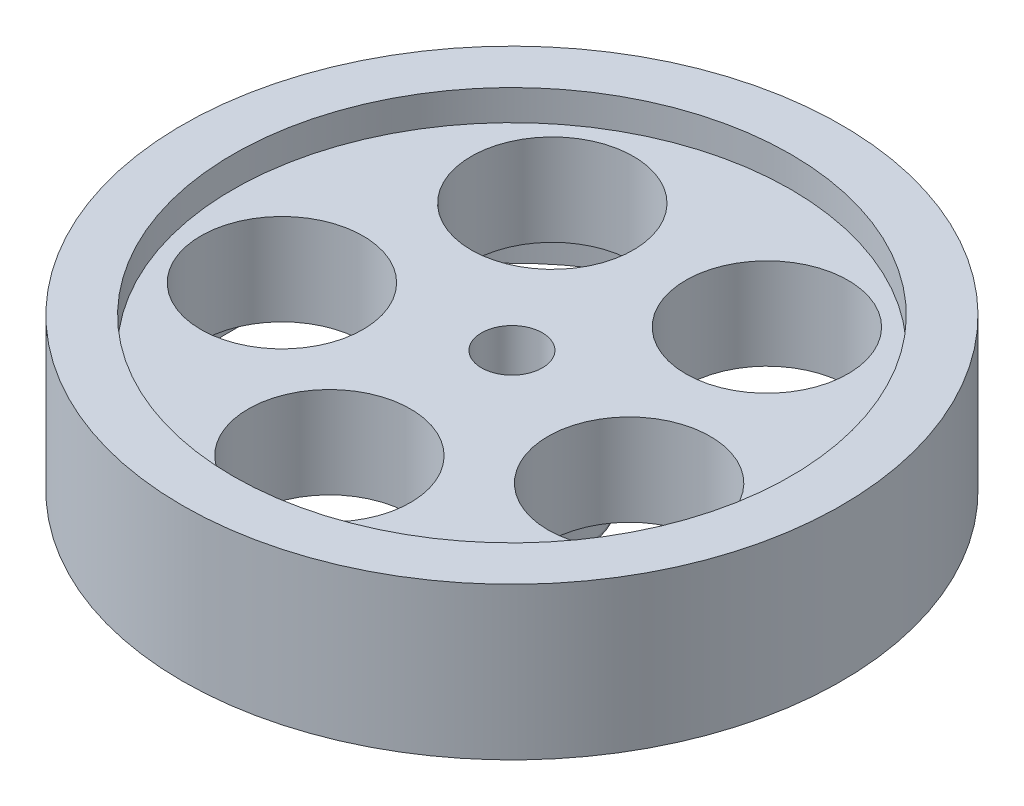
SolidWorks part; units mm, degrees
ref_plane "Front Plane" through (0, 0, 0) normal (0, 0, 1) x (1, 0, 0)
ref_plane "Top Plane" through (0, 0, 0) normal (0, 1, 0) x (1, 0, 0)
ref_plane "Right Plane" through (0, 0, 0) normal (1, 0, 0) x (0, 0, -1)
sketch "Sketch2" plane through (0, 0, 0) normal (0, 1, 0) x (1, 0, 0)
  circle A0 centre (0, 0) radius 32.5
extrude "Boss-Extrude1" add sketch "Sketch2" along normal blind 15
sketch "Sketch3" plane through (0, 15, 0) normal (0, 1, 0) x (1, 0, 0)
  circle A0 centre (0, 0) radius 27.5
  dimension "D1" = 55
extrude "Cut-Extrude1" cut sketch "Sketch3" against normal blind 3
extrude "Cut-Extrude2" cut sketch "Sketch3<2>" along normal blind 3 from offset 15 offset against normal yes
sketch "Sketch3<2>" plane through (0, 15, 0) normal (0, 1, 0) x (1, 0, 0) same geometry as "Sketch3"
sketch "Sketch4" plane through (0, 3, 0) normal (0, -1, 0) x (1, 0, 0)
  line L0 (0, 0) -> (0, 27.5) construction
  circle A0 centre (0, 0) radius 27.5 construction
  circle A1 centre (0, 18) radius 8
  circle A2 centre (17.119, 5.5623) radius 8
  circle A3 centre (10.5801, -14.5623) radius 8
  circle A4 centre (-10.5801, -14.5623) radius 8
  circle A5 centre (-17.119, 5.5623) radius 8
  point P18 (0, 0)
  dimension "D1" = 18
  dimension "D2" = 5
extrude "Cut-Extrude3" cut sketch "Sketch4" against normal through all both and the other way through all
sketch "Sketch5" plane through (0, 3, 0) normal (0, -1, 0) x (1, 0, 0)
  circle A0 centre (0, 0) radius 7.2734
extrude "Boss-Extrude2" add sketch "Sketch5" along normal blind 4.5
fillet "Fillet3" radius 0.5 1 edges at (0, -1.5, -7.2734)
sketch "Sketch6" plane through (0, -1.5, 0) normal (0, -1, 0) x (1, 0, 0)
  circle A0 centre (0, 0) radius 3
  dimension "D1" = 6
extrude "Cut-Extrude4" cut sketch "Sketch6" against normal through all both and the other way through all
